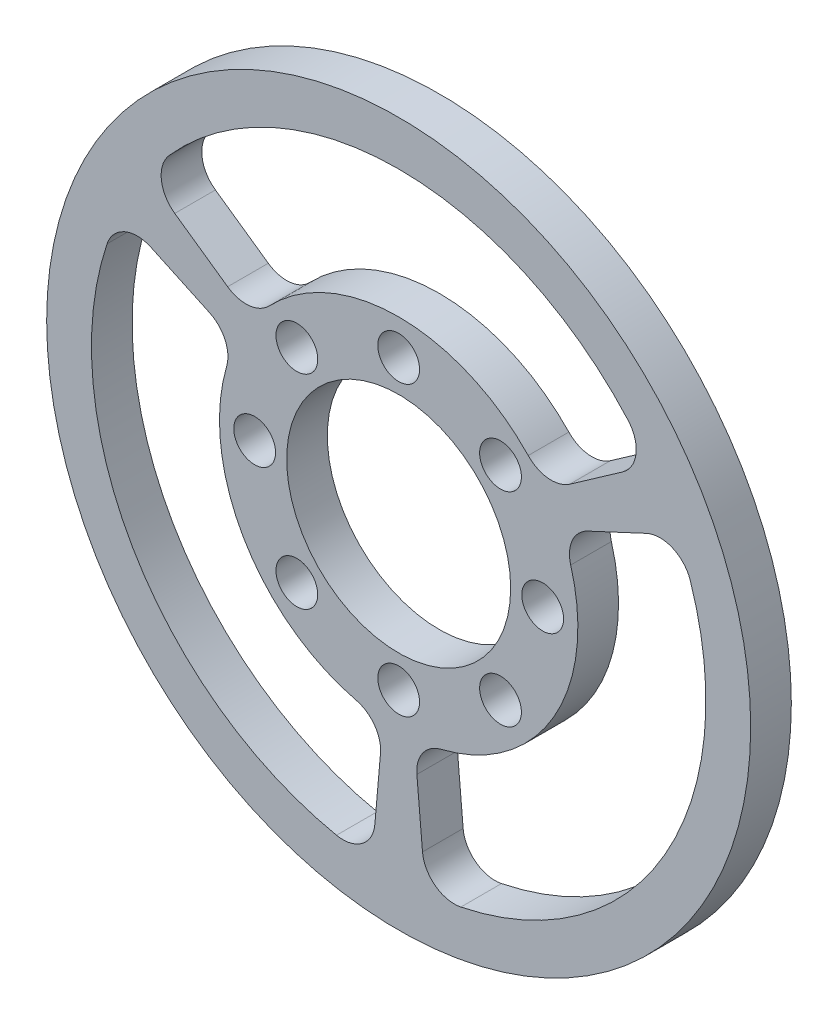
SolidWorks part; units mm, degrees
material "Tungsten"
ref_plane "Front Plane" through (0, 0, 0) normal (0, 0, 1) x (1, 0, 0)
ref_plane "Top Plane" through (0, 0, 0) normal (0, 1, 0) x (1, 0, 0)
ref_plane "Right Plane" through (0, 0, 0) normal (1, 0, 0) x (0, 0, -1)
sketch "Sketch1" plane through (0, 0, 0) normal (0, 0, 1) x (1, 0, 0)
  line L0 (0, 0) -> (0, 22.5) construction
  line L1 (0, 0) -> (-39.3193, 27.5317) construction
  line L2 (0, 0) -> (39.3193, 27.5317) construction
  line L3 (-39.3193, 27.5317) -> (-22.9363, 16.0601)
  line L4 (39.3193, 27.5317) -> (22.9363, 16.0601)
  line L5 (43.5028, 20.2857) -> (25.3766, 11.8333)
  line L6 (4.1835, -47.8173) -> (2.4404, -27.8935)
  line L7 (-4.1835, -47.8173) -> (-2.4404, -27.8935)
  line L8 (-43.5028, 20.2857) -> (-25.3766, 11.8333)
  circle A0 centre (0, 0) radius 55
  circle A1 centre (0, 0) radius 22.5 construction
  circle A2 centre (0, 22.5) radius 3.2639
  circle A3 centre (15.9099, 15.9099) radius 3.2639
  circle A4 centre (22.5, 0) radius 3.2639
  circle A5 centre (15.9099, -15.9099) radius 3.2639
  circle A6 centre (0, -22.5) radius 3.2639
  circle A7 centre (-15.9099, -15.9099) radius 3.2639
  circle A8 centre (-22.5, 0) radius 3.2639
  circle A9 centre (-15.9099, 15.9099) radius 3.2639
  arc A10 (-39.3193, 27.5317) -> (39.3193, 27.5317) centre (0, 0) cw
  arc A11 (-22.9363, 16.0601) -> (22.9363, 16.0601) centre (0, 0) cw
  arc A12 (43.5028, 20.2857) -> (4.1835, -47.8173) centre (0, 0) cw
  arc A13 (25.3766, 11.8333) -> (2.4404, -27.8935) centre (0, 0) cw
  arc A14 (-4.1835, -47.8173) -> (-43.5028, 20.2857) centre (0, 0) cw
  arc A15 (-2.4404, -27.8935) -> (-25.3766, 11.8333) centre (0, 0) cw
  circle A16 centre (0, 0) radius 17.5
  point P4 (0, 22.5)
  point P8 (15.9099, 15.9099)
  point P9 (22.5, 0)
  point P10 (15.9099, -15.9099)
  point P11 (0, -22.5)
  point P12 (-15.9099, -15.9099)
  point P13 (-22.5, 0)
  point P14 (-15.9099, 15.9099)
  point P15 (0, 0)
  point P43 (0, 0)
  dimension "D1" = 110
  dimension "D2" = 45
  dimension "D4" = 6.5278
  dimension "D6" = 28
  dimension "D7" = 20
  dimension "D9" = 35
  dimension "D5" = 110
  dimension "D3" = 8
  dimension "D8" = 3
extrude "Boss-Extrude1" add sketch "Sketch1" along normal blind 6.35
fillet "Fillet1" radius 5 12 edges at (-2.4404, -27.8935, 3.175) (-25.3766, 11.8333, 3.175) (-43.5028, 20.2857, 3.175) (25.3766, 11.8333, 3.175) (2.4404, -27.8935, 3.175) (4.1835, -47.8173, 3.175) (43.5028, 20.2857, 3.175) (-22.9363, 16.0601, 3.175) (22.9363, 16.0601, 3.175) (39.3193, 27.5317, 3.175) (-39.3193, 27.5317, 3.175) (-4.1835, -47.8173, 3.175)
